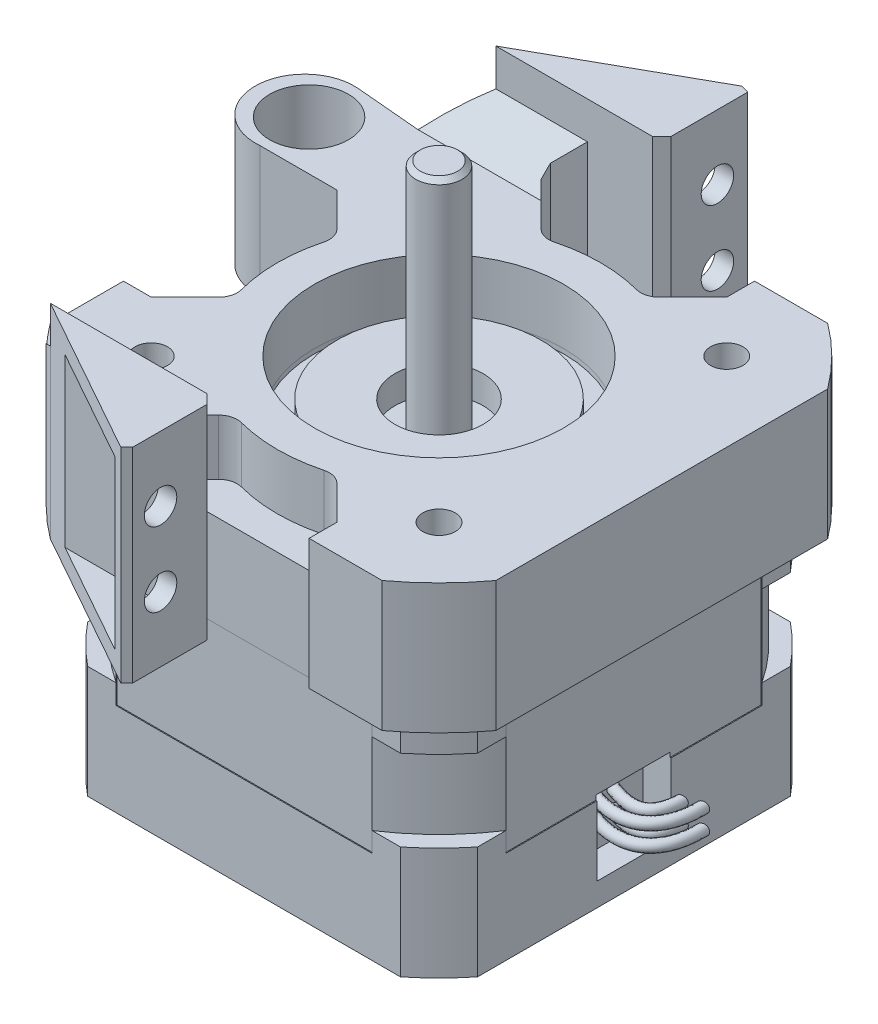
SolidWorks part; units mm, degrees
ref_plane "Front Plane" through (0, 0, 0) normal (0, 0, 1) x (1, 0, 0)
ref_plane "Top Plane" through (0, 0, 0) normal (0, 1, 0) x (1, 0, 0)
ref_plane "Right Plane" through (0, 0, 0) normal (1, 0, 0) x (0, 0, -1)
sketch "Sketch1" plane through (0, 0, 0) normal (0, 1, 0) x (1, 0, 0)
  line L0 (0, -21) -> (0, 21) construction
  line L1 (-21, 16.851) -> (-21, -16.851)
  line L2 (-16.851, -21) -> (16.851, -21)
  line L3 (21, -16.851) -> (21, 16.851)
  line L4 (16.851, 21) -> (-16.851, 21)
  line L5 (-21, 0) -> (21, 0) construction
  arc A0 (-21, 16.851) -> (-16.851, 21) centre (0, 0) cw
  arc A1 (16.851, 21) -> (21, 16.851) centre (0, 0) cw
  arc A2 (21, -16.851) -> (16.851, -21) centre (0, 0) cw
  arc A3 (-21, -16.851) -> (-16.851, -21) centre (0, 0) ccw
  dimension "D3" = 26.925
  dimension "D1" = 42
  dimension "D2" = 42
extrude "Boss-Extrude2" add sketch "Sketch1" along normal blind 33
sketch "Sketch3" plane through (0, 0, 0) normal (0, 0, 1) x (1, 0, 0)
  line L0 (0, -2.0131) -> (0, 34.8611) construction
  line L1 (-30.125, 20.875) -> (-25.125, 20.875)
  line L2 (-30.125, 20.875) -> (-30.125, 12.125)
  line L3 (-30.125, 12.125) -> (-25.125, 12.125)
  line L4 (-25.125, 20.875) -> (-25.125, 12.125)
  line L5 (21, 16.5) -> (-21, 16.5) construction
  line L6 (21, 33) -> (21, 0) construction
  line L7 (-21, 33) -> (-21, 0) construction
  point P13 (-25.125, 16.5)
  dimension "D1" = 8.75
  dimension "D2" = 25.125
  dimension "D3" = 5
revolve "Cut-Revolve1" cut sketch "Sketch3" angle 360 about L0
sketch "Sketch4" plane through (0, 33, 0) normal (0, 1, 0) x (1, 0, 0)
  circle A0 centre (0, 0) radius 13.425
  dimension "D1" = 26.85
extrude "Cut-Extrude1" cut sketch "Sketch4" against normal blind 0.5
sketch "Sketch5" plane through (0, 32.5, 0) normal (0, 1, 0) x (1, 0, 0)
  circle A0 centre (0, 0) radius 11
  dimension "D1" = 22
extrude "Boss-Extrude3" add sketch "Sketch5" along normal blind 2.5
sketch "Sketch6" plane through (0, 35, 0) normal (0, 1, 0) x (1, 0, 0)
  circle A0 centre (0, 0) radius 4.75
  dimension "D1" = 9.5
extrude "Cut-Extrude2" cut sketch "Sketch6" against normal blind 3
sketch "Sketch7" plane through (0, 32, 0) normal (0, 1, 0) x (1, 0, 0)
  circle A0 centre (0, 0) radius 2.5
  dimension "D1" = 5
extrude "Boss-Extrude4" add sketch "Sketch7" along normal blind 25.25
chamfer "Chamfer1" distance 0.5 angle 45 1 edges at (0, 57.25, 2.5)
sketch "Sketch8" plane through (0, 0, 0) normal (0, -1, 0) x (1, 0, 0)
  circle A0 centre (0, 0) radius 4.5
  dimension "D1" = 9
extrude "Cut-Extrude3" cut sketch "Sketch8" against normal blind 3
sketch "Sketch9" plane through (0, 33, 0) normal (0, 1, 0) x (1, 0, 0)
  line L0 (-15.5, 15.5) -> (15.5, 15.5) construction
  line L1 (15.5, 15.5) -> (15.5, -15.5) construction
  line L2 (15.5, -15.5) -> (-15.5, -15.5) construction
  line L3 (-15.5, -15.5) -> (-15.5, 15.5) construction
  point P2 (-15.5, 0)
  point P5 (0, 15.5)
  dimension "D1" = 31
  dimension "D2" = 31
hole_wizard "M3x0.5 Tapped Hole1" positions "Sketch11" profile "Sketch10" tap size "M3x0.5" standard "ANSI Metric"
sketch "Sketch11" plane through (0, 33, 0) normal (0, 1, 0) x (1, 0, 0)
  point P0 (-15.5, -15.5)
  point P3 (-15.5, 15.5)
  point P6 (15.5, 15.5)
  point P9 (15.5, -15.5)
sketch "Sketch10" plane through (-15.5, 33, 15.5) normal (1, 0, 0) x (0, 0, 1)
  line L0 (0, 0) -> (0, 5.2511)
  line L1 (0, 5.2511) -> (1.25, 4.5)
  line L2 (1.25, 4.5) -> (1.25, 0)
  line L5 (1.25, 0) -> (0, 0)
  line L10 (0, 5.2511) -> (-1.25, 4.5) construction
  line L11 (0, -6.35) -> (0, 107.95) construction
  dimension "Tap Drill Dia." = 2.5
  dimension "Tap Drill Depth" = 4.5
  dimension "Drill Angle" = 118
sketch "Sketch12" plane through (21, 0, 0) normal (1, 0, 0) x (0, 0, -1)
  line L0 (-16.851, 0) -> (16.851, 0) construction
  line L1 (-4, 10.5) -> (4, 10.5)
  line L2 (-4, 10.5) -> (-4, 2.5)
  line L3 (-4, 2.5) -> (4, 2.5)
  line L4 (4, 10.5) -> (4, 2.5)
  point P4 (0, 2.5)
  dimension "D1" = 8
  dimension "D2" = 8
  dimension "D3" = 2.5
extrude "Cut-Extrude4" cut sketch "Sketch12" against normal blind 3
sketch "Sketch13" plane through (18, 0, 0) normal (1, 0, 0) x (0, 0, -1)
  circle A0 centre (-1.1125, 7.415) radius 0.6
  circle A1 centre (0.707, 7.415) radius 0.6
  circle A2 centre (-1.1125, 5.3322) radius 0.6
  circle A3 centre (0.707, 5.3322) radius 0.6
  dimension "D1" = 1.2
sketch "Sketch14" plane through (0, 0, 0) normal (0, 1, 0) x (1, 0, 0)
  spline S0 degree 2 poles (17.6767, 0) (23.6461, -2.3668) (23.7984, 3.3576) knots 0 0 0 1 1 1
sweep "Sweep2" add profiles "Sketch13" path "Sketch14"
sketch "Sketch15" plane through (0, 0, -21) normal (0, 0, -1) x (-1, 0, 0)
  line L0 (-13.7937, 12.125) -> (-13.7937, 20.875) construction
  line L1 (-13.7937, 23) -> (13.7937, 23)
  line L2 (-13.7937, 23) -> (-13.7937, 10)
  line L3 (-13.7937, 10) -> (13.7937, 10)
  line L4 (13.7937, 23) -> (13.7937, 10)
  line L5 (13.7937, 20.875) -> (13.7937, 12.125) construction
  point P8 (-13.7937, 16.5)
  point P9 (-13.7937, 16.5)
  dimension "D1" = 13
extrude "Cut-Extrude5" cut sketch "Sketch15" against normal blind 0.1
ref_axis "Axis1" through (0, 0, 0) along (0, 1, 0)
pattern_circular "CirPattern1" count 4 over 360 about axis through (0, 0, 0) along (0, 1, 0) of "Cut-Extrude5"
ref_plane "Plane1" through (0, 33, 0) normal (0, 1, 0) x (1, 0, 0)
sketch "Sketch16" plane through (0, 33, 0) normal (0, 1, 0) x (1, 0, 0)
  line L0 (-10.001, -21) -> (-5.5264, -16.5254)
  line L1 (9.999, -21) -> (5.5249, -16.5259)
  line L2 (-21, -9.999) -> (-16.5259, -5.5249)
  line L3 (-16.5254, 5.5264) -> (-21, 10.001)
  line L4 (-21, 16.851) -> (-21, -16.851)
  line L5 (-16.851, -21) -> (16.851, -21)
  line L6 (21, -16.851) -> (21, 16.851)
  line L7 (16.851, 21) -> (-16.851, 21)
  line L8 (-21, 16.851) -> (-21, -16.851)
  line L9 (-16.851, -21) -> (16.851, -21)
  line L10 (21, -16.851) -> (21, 16.851)
  line L11 (16.851, 21) -> (-16.851, 21)
  line L12 (-10.001, 21) -> (-5.5264, 16.5254)
  line L13 (9.999, 21) -> (5.5249, 16.5259)
  circle A0 centre (0, 0) radius 13.425 construction
  circle A1 centre (0, 0) radius 13.425
  arc A4 (-16.851, 21) -> (-21, 16.851) centre (0, 0) ccw
  arc A5 (-21, -16.851) -> (-16.851, -21) centre (0, 0) ccw
  arc A6 (16.851, -21) -> (21, -16.851) centre (0, 0) ccw
  arc A7 (21, 16.851) -> (16.851, 21) centre (0, 0) ccw
  arc A8 (-16.851, 21) -> (-21, 16.851) centre (0, 0) ccw
  arc A9 (-21, -16.851) -> (-16.851, -21) centre (0, 0) ccw
  arc A10 (16.851, -21) -> (21, -16.851) centre (0, 0) ccw
  arc A11 (21, 16.851) -> (16.851, 21) centre (0, 0) ccw
  circle A12 centre (-15.5, -15.5) radius 1.25 construction
  circle A13 centre (15.5, -15.5) radius 1.25 construction
  circle A14 centre (15.5, 15.5) radius 1.25 construction
  circle A15 centre (-15.5, 15.5) radius 1.25 construction
  circle A16 centre (-15.5, -15.5) radius 1.25
  circle A17 centre (15.5, -15.5) radius 1.25
  circle A18 centre (15.5, 15.5) radius 1.25
  circle A19 centre (-15.5, 15.5) radius 1.25
  circle A20 centre (-15.5, 15.5) radius 1.75
  circle A21 centre (-15.5, -15.5) radius 1.75
  circle A22 centre (15.5, -15.5) radius 1.75
  circle A23 centre (15.5, 15.5) radius 1.75
  circle A24 centre (0, 0) radius 17.425
  dimension "D4" = 20
  dimension "D5" = 45
  dimension "D6" = 45
  dimension "D7" = 6.85
  dimension "D8" = 45
  dimension "D9" = 45
  dimension "D10" = 20
  dimension "D11" = 6.85
  dimension "D12" = 45
  dimension "D13" = 45
  dimension "D14" = 20
  dimension "D15" = 6.85
  dimension "D1" = 0
  dimension "D2" = 0.5
  dimension "D3" = 4
extrude "Boss-Extrude5" add sketch "Sketch16" along normal blind 6 separate body contours A24 L2 L8 A9 L9 L0 A21 | A24 A1 | A24 L12 L11 A8 L8 L3 A20 | A24 L1 L9 A10 L10 A11 L11 L13 A23 A22 region at (-13.426, 33, 20.7812) region at (-11.9734, 33, 11.9723) region at (8.0785, 33, 18.4465) region at (-18.608, 33, -7.9184)
sketch "Sketch17" plane through (0, 39, 0) normal (0, 1, 0) x (1, 0, 0)
  line L13 (-21, 10.001) -> (-24, 10.001)
  line L14 (-10.001, 21) -> (-10.001, 24)
  line L15 (9.999, 21) -> (9.999, 24)
  line L16 (-21, -9.999) -> (-24, -9.999)
  line L17 (-10.001, -21) -> (-10.001, -24)
  line L18 (9.999, -21) -> (9.999, -24)
  line L26 (-8.7583, -24) -> (-4.6476, -19.8892)
  line L27 (4.646, -19.8896) -> (8.7564, -24)
  line L28 (8.7564, -24) -> (17.8747, -24)
  line L29 (24, -17.8747) -> (24, 17.8747)
  line L30 (17.8747, 24) -> (8.7564, 24)
  line L31 (8.7564, 24) -> (4.646, 19.8896)
  line L32 (-4.6476, 19.8892) -> (-8.7583, 24)
  line L33 (-8.7583, 24) -> (-17.8747, 24)
  line L34 (-24, 17.8747) -> (-24, 8.7583)
  line L35 (-24, 8.7583) -> (-19.8892, 4.6476)
  line L36 (-19.8896, -4.646) -> (-24, -8.7564)
  line L37 (-24, -8.7564) -> (-24, -17.8747)
  line L38 (-17.8747, -24) -> (-8.7583, -24)
  line L39 (-8.7583, -24) -> (-4.6476, -19.8892)
  line L40 (4.646, -19.8896) -> (8.7564, -24)
  line L41 (8.7564, -24) -> (17.8747, -24)
  line L42 (24, -17.8747) -> (24, 17.8747)
  line L43 (17.8747, 24) -> (8.7564, 24)
  line L44 (8.7564, 24) -> (4.646, 19.8896)
  line L45 (-4.6476, 19.8892) -> (-8.7583, 24)
  line L46 (-8.7583, 24) -> (-17.8747, 24)
  line L47 (-24, 17.8747) -> (-24, 8.7583)
  line L48 (-24, 8.7583) -> (-19.8892, 4.6476)
  line L49 (-19.8896, -4.646) -> (-24, -8.7564)
  line L50 (-24, -8.7564) -> (-24, -17.8747)
  line L51 (-17.8747, -24) -> (-8.7583, -24)
  line L71 (-9.7939, -21.5) -> (-5.3895, -17.0956)
  line L72 (5.388, -17.0961) -> (9.7919, -21.5)
  line L73 (9.7919, -21.5) -> (17.0259, -21.5)
  line L74 (21.5, -17.0259) -> (21.5, 17.0259)
  line L75 (17.0259, 21.5) -> (9.7919, 21.5)
  line L76 (9.7919, 21.5) -> (5.388, 17.0961)
  line L77 (-5.3895, 17.0956) -> (-9.7939, 21.5)
  line L78 (-9.7939, 21.5) -> (-17.0259, 21.5)
  line L79 (-21.5, 17.0259) -> (-21.5, 9.7939)
  line L80 (-21.5, 9.7939) -> (-17.0956, 5.3895)
  line L81 (-17.0961, -5.388) -> (-21.5, -9.7919)
  line L82 (-21.5, -9.7919) -> (-21.5, -17.0259)
  line L83 (-17.0259, -21.5) -> (-9.7939, -21.5)
  line L84 (-9.7939, -21.5) -> (-5.3895, -17.0956)
  line L85 (5.388, -17.0961) -> (9.7919, -21.5)
  line L86 (9.7919, -21.5) -> (17.0259, -21.5)
  line L87 (21.5, -17.0259) -> (21.5, 17.0259)
  line L88 (17.0259, 21.5) -> (9.7919, 21.5)
  line L89 (9.7919, 21.5) -> (5.388, 17.0961)
  line L90 (-5.3895, 17.0956) -> (-9.7939, 21.5)
  line L91 (-9.7939, 21.5) -> (-17.0259, 21.5)
  line L92 (-21.5, 17.0259) -> (-21.5, 9.7939)
  line L93 (-21.5, 9.7939) -> (-17.0956, 5.3895)
  line L94 (-17.0961, -5.388) -> (-21.5, -9.7919)
  line L95 (-21.5, -9.7919) -> (-21.5, -17.0259)
  line L96 (-17.0259, -21.5) -> (-9.7939, -21.5)
  arc A14 (-4.6476, -19.8892) -> (4.646, -19.8896) centre (0, 0) ccw
  arc A15 (17.8747, -24) -> (24, -17.8747) centre (0, 0) ccw
  arc A16 (24, 17.8747) -> (17.8747, 24) centre (0, 0) ccw
  arc A17 (4.646, 19.8896) -> (-4.6476, 19.8892) centre (0, 0) ccw
  arc A18 (-17.8747, 24) -> (-24, 17.8747) centre (0, 0) ccw
  arc A19 (-19.8892, 4.6476) -> (-19.8896, -4.646) centre (0, 0) ccw
  arc A20 (-24, -17.8747) -> (-17.8747, -24) centre (0, 0) ccw
  arc A21 (-4.6476, -19.8892) -> (4.646, -19.8896) centre (0, 0) ccw
  arc A22 (17.8747, -24) -> (24, -17.8747) centre (0, 0) ccw
  arc A23 (24, 17.8747) -> (17.8747, 24) centre (0, 0) ccw
  arc A24 (4.646, 19.8896) -> (-4.6476, 19.8892) centre (0, 0) ccw
  arc A25 (-17.8747, 24) -> (-24, 17.8747) centre (0, 0) ccw
  arc A26 (-19.8892, 4.6476) -> (-19.8896, -4.646) centre (0, 0) ccw
  arc A27 (-24, -17.8747) -> (-17.8747, -24) centre (0, 0) ccw
  arc A36 (-5.3895, -17.0956) -> (5.388, -17.0961) centre (0, 0) ccw
  arc A37 (17.0259, -21.5) -> (21.5, -17.0259) centre (0, 0) ccw
  arc A38 (21.5, 17.0259) -> (17.0259, 21.5) centre (0, 0) ccw
  arc A39 (5.388, 17.0961) -> (-5.3895, 17.0956) centre (0, 0) ccw
  arc A40 (-17.0259, 21.5) -> (-21.5, 17.0259) centre (0, 0) ccw
  arc A41 (-17.0956, 5.3895) -> (-17.0961, -5.388) centre (0, 0) ccw
  arc A42 (-21.5, -17.0259) -> (-17.0259, -21.5) centre (0, 0) ccw
  arc A43 (-5.3895, -17.0956) -> (5.388, -17.0961) centre (0, 0) ccw
  arc A44 (17.0259, -21.5) -> (21.5, -17.0259) centre (0, 0) ccw
  arc A45 (21.5, 17.0259) -> (17.0259, 21.5) centre (0, 0) ccw
  arc A46 (5.388, 17.0961) -> (-5.3895, 17.0956) centre (0, 0) ccw
  arc A47 (-17.0259, 21.5) -> (-21.5, 17.0259) centre (0, 0) ccw
  arc A48 (-17.0956, 5.3895) -> (-17.0961, -5.388) centre (0, 0) ccw
  arc A49 (-21.5, -17.0259) -> (-17.0259, -21.5) centre (0, 0) ccw
  line M24 (9.999, -21) -> (16.851, -21)
  arc M25 (16.851, -21) -> (21, -16.851) centre (0, 0) ccw
  line M26 (21, -16.851) -> (21, 16.851)
  arc M27 (21, 16.851) -> (16.851, 21) centre (0, 0) ccw
  line M28 (16.851, 21) -> (9.999, 21)
  line M32 (-10.001, 21) -> (-16.851, 21)
  arc M33 (-16.851, 21) -> (-21, 16.851) centre (0, 0) ccw
  line M34 (-21, 16.851) -> (-21, 10.001)
  line M38 (-21, -9.999) -> (-21, -16.851)
  arc M39 (-21, -16.851) -> (-16.851, -21) centre (0, 0) ccw
  line M40 (-16.851, -21) -> (-10.001, -21)
  dimension "D1" = 3
  dimension "D2" = 0.5
extrude "Boss-Extrude6" add sketch "Sketch17" against normal blind 14 separate body contours L46 A25 L47 L13 L14 M34 M33 M32 | L50 A27 L51 L17 L16 M40 M39 M38 | L42 A23 L43 L15 L18 L41 A22 M28 M27 M26 M25 M24 region at (-22.75, 39, -10.199) region at (-21.698, 39, 13.5124) region at (10.499, 39, -22.75)
fillet "Fillet1" radius 2 6 edges at (5.5249, 36, 16.5259) (-5.5264, 36, 16.5254) (-16.5259, 36, 5.5249) (-16.5254, 36, -5.5264) (5.5249, 36, -16.5259) (-5.5264, 36, -16.5254)
extrude "Boss-Extrude7" add sketch "Sketch17<4>" against normal up to vertex (6 mm away) separate body contours L95 A49 L96 L17 L16 M40 M39 M38 | L91 A47 L92 L13 L14 M34 M33 M32 | L87 A45 L88 L15 L18 L86 A44 M28 M27 M26 M25 M24 region at (-21.25, 39, -10.1636) region at (-21.25, 39, 10.1617) region at (13.5124, 39, -21.0549) up to point (-17.3686, 33, 6.3676)
sketch "Sketch17<4>" plane through (0, 39, 0) normal (0, 1, 0) x (1, 0, 0) same geometry as "Sketch17"
combine bodies "Combine2" operation type add bodies to combine 115 122 121 114 116 117 120
sketch "Sketch18" plane through (0, 39, 0) normal (0, 1, 0) x (1, 0, 0)
  line L0 (-10.001, 24) -> (-0.001, 24)
  line L1 (-0.001, 24) -> (-0.001, 34)
  line L3 (-17.8747, 24) -> (-0.001, 34)
  line L4 (-17.8747, -24) -> (-0.001, -24)
  line L5 (-10.001, -21) -> (-10.001, -24) construction
  line L6 (-0.001, -24) -> (-0.001, -34)
  line L7 (-0.001, -34) -> (-17.8747, -24)
  line L23 (9.999, 24) -> (9.999, 21)
  line L24 (9.999, 21) -> (6.3676, 17.3686)
  line L25 (-6.3692, 17.3682) -> (-10.001, 21)
  line L26 (-10.001, 21) -> (-10.001, 24)
  line L27 (-10.001, 24) -> (-17.8747, 24)
  line L28 (-24, 17.8747) -> (-24, 10.001)
  line L29 (-24, 10.001) -> (-21, 10.001)
  line L30 (-21, 10.001) -> (-17.3682, 6.3692)
  line L31 (-17.3686, -6.3676) -> (-21, -9.999)
  line L32 (-21, -9.999) -> (-24, -9.999)
  line L33 (-24, -9.999) -> (-24, -17.8747)
  line L34 (-17.8747, -24) -> (-10.001, -24)
  line L35 (-10.001, -24) -> (-10.001, -21)
  line L36 (-10.001, -21) -> (-6.3692, -17.3682)
  line L37 (6.3676, -17.3686) -> (9.999, -21)
  line L38 (9.999, -21) -> (9.999, -24)
  line L39 (9.999, -24) -> (17.8747, -24)
  line L40 (24, -17.8747) -> (24, 17.8747)
  line L41 (17.8747, 24) -> (9.999, 24)
  line L46 (-10.001, 24) -> (-17.8747, 24)
  arc A15 (4.4434, 16.8489) -> (6.3676, 17.3686) centre (4.9534, 18.7828) ccw
  arc A16 (4.4434, 16.8489) -> (-4.4448, 16.8486) centre (0, 0) ccw
  arc A17 (-6.3692, 17.3682) -> (-4.4448, 16.8486) centre (-4.955, 18.7824) ccw
  arc A18 (-17.8747, 24) -> (-24, 17.8747) centre (0, 0) ccw
  arc A19 (-16.8486, 4.4448) -> (-17.3682, 6.3692) centre (-18.7824, 4.955) ccw
  arc A20 (-16.8486, 4.4448) -> (-16.8489, -4.4434) centre (0, 0) ccw
  arc A21 (-17.3686, -6.3676) -> (-16.8489, -4.4434) centre (-18.7828, -4.9534) ccw
  arc A22 (-24, -17.8747) -> (-17.8747, -24) centre (0, 0) ccw
  arc A23 (-4.4448, -16.8486) -> (-6.3692, -17.3682) centre (-4.955, -18.7824) ccw
  arc A24 (-4.4448, -16.8486) -> (4.4434, -16.8489) centre (0, 0) ccw
  arc A25 (6.3676, -17.3686) -> (4.4434, -16.8489) centre (4.9534, -18.7828) ccw
  arc A26 (17.8747, -24) -> (24, -17.8747) centre (0, 0) ccw
  arc A27 (24, 17.8747) -> (17.8747, 24) centre (0, 0) ccw
  dimension "D3" = 10
  dimension "D1" = 10
  dimension "D2" = 10
  dimension "D4" = 10
  dimension "D5" = 0
extrude "Boss-Extrude8" add sketch "Sketch18" against normal up to surface (14 mm away) up to face at (-18.2819, 25, -18.2819)
sketch "Sketch19" plane through (-0.001, 0, 0) normal (1, 0, 0) x (0, 0, -1)
  line L0 (34, 25) -> (34, 39) construction
  line L1 (34, 27) -> (26, 27)
  line L2 (34, 27) -> (34, 37)
  line L3 (34, 37) -> (26, 37)
  line L4 (26, 27) -> (26, 37)
  line L5 (24, 39) -> (34, 39) construction
  line L6 (-34, 25) -> (-34, 39) construction
  line L7 (-34, 37) -> (-26, 37)
  line L8 (-34, 37) -> (-34, 27)
  line L9 (-34, 27) -> (-26, 27)
  line L10 (-26, 37) -> (-26, 27)
  line L11 (-34, 39) -> (-24, 39) construction
  circle A0 centre (30, 32) radius 1.75
  circle A1 centre (-30, 32) radius 1.75
  point P19 (34, 32)
  point P20 (-34, 32)
  point P21 (30, 27)
  point P25 (-30, 27)
  dimension "D7" = 3.5
  dimension "D8" = 3.5
  dimension "D1" = 10
  dimension "D2" = 2
  dimension "D3" = 8
  dimension "D4" = 8
  dimension "D5" = 10
  dimension "D6" = 2
ref_plane "Plane2" through (-2.001, 0, 0) normal (1, 0, 0) x (0, 0, -1)
sketch "Sketch20" plane through (-2.001, 0, 0) normal (1, 0, 0) x (0, 0, -1)
  line L0 (34, 27) -> (34, 37) construction
  line L1 (34, 37) -> (26, 37) construction
  line L2 (34, 27) -> (26, 27) construction
  line L3 (26, 27) -> (26, 37) construction
  line L4 (-34, 37) -> (-34, 27) construction
  line L5 (-34, 37) -> (-26, 37) construction
  line L6 (-26, 37) -> (-26, 27) construction
  line L7 (-34, 27) -> (-26, 27) construction
  line L8 (34, 27) -> (34, 37)
  line L9 (34, 37) -> (26, 37)
  line L10 (34, 27) -> (26, 27)
  line L11 (26, 27) -> (26, 37)
  line L12 (-34, 37) -> (-34, 27)
  line L13 (-34, 37) -> (-26, 37)
  line L14 (-26, 37) -> (-26, 27)
  line L15 (-34, 27) -> (-26, 27)
  circle A0 centre (-30, 32) radius 1.75 construction
  circle A1 centre (30, 32) radius 1.75 construction
  circle A2 centre (-30, 32) radius 1.75
  circle A3 centre (30, 32) radius 1.75
extrude "Cut-Extrude7" cut sketch "Sketch20" against normal blind 34 contours L12 L15 L14 L13 A2 | A2 | L10 L11 L9 L8 region at (-2.001, 36.8719, 30)
chamfer "Chamfer2" distance 2 angle 45 2 edges at (-10.001, 32, 24) (-10.001, 32, -24)
ref_plane "Plane3" [suppressed] through (-2.001, 37, 32.881) normal (0, 0, 1) x (1, 0, 0)
extrude "Cut-Extrude10" cut sketch "Sketch19" against normal blind 10 contours A0 | A1
sketch "Sketch21" plane through (0, 39, 0) normal (0, 1, 0) x (1, 0, 0)
  line L0 (-17.8747, -24) -> (-8.001, -24)
  line L1 (-8.001, 24) -> (-17.8747, 24)
  line L25 (9.999, 24) -> (9.999, 21)
  line L26 (9.999, 21) -> (6.3676, 17.3686)
  line L27 (-6.3692, 17.3682) -> (-10.001, 21)
  line L28 (-10.001, 21) -> (-10.001, 22)
  line L29 (-10.001, 22) -> (-8.001, 24)
  line L30 (-8.001, 24) -> (-0.001, 24)
  line L31 (-0.001, 24) -> (-0.001, 34)
  line L32 (-0.001, 34) -> (-17.8747, 24)
  line L33 (-24, 17.8747) -> (-24, 10.001)
  line L34 (-24, 10.001) -> (-21, 10.001)
  line L35 (-21, 10.001) -> (-17.3682, 6.3692)
  line L36 (-17.3686, -6.3676) -> (-21, -9.999)
  line L37 (-21, -9.999) -> (-24, -9.999)
  line L38 (-24, -9.999) -> (-24, -17.8747)
  line L39 (-17.8747, -24) -> (-0.001, -34)
  line L40 (-0.001, -34) -> (-0.001, -24)
  line L41 (-0.001, -24) -> (-8.001, -24)
  line L42 (-8.001, -24) -> (-10.001, -22)
  line L43 (-10.001, -22) -> (-10.001, -21)
  line L44 (-10.001, -21) -> (-6.3692, -17.3682)
  line L45 (6.3676, -17.3686) -> (9.999, -21)
  line L46 (9.999, -21) -> (9.999, -24)
  line L47 (9.999, -24) -> (17.8747, -24)
  line L48 (24, -17.8747) -> (24, 17.8747)
  line L49 (17.8747, 24) -> (9.999, 24)
  line L50 (9.999, 24) -> (9.999, 21)
  line L51 (9.999, 21) -> (6.3676, 17.3686)
  line L52 (-6.3692, 17.3682) -> (-10.001, 21)
  line L53 (-10.001, 21) -> (-10.001, 22)
  line L54 (-10.001, 22) -> (-8.001, 24)
  line L55 (-8.001, 24) -> (-0.001, 24)
  line L56 (-0.001, 24) -> (-0.001, 34)
  line L57 (-0.001, 34) -> (-17.8747, 24)
  line L58 (-24, 17.8747) -> (-24, 10.001)
  line L59 (-24, 10.001) -> (-21, 10.001)
  line L60 (-21, 10.001) -> (-17.3682, 6.3692)
  line L61 (-17.3686, -6.3676) -> (-21, -9.999)
  line L62 (-21, -9.999) -> (-24, -9.999)
  line L63 (-24, -9.999) -> (-24, -17.8747)
  line L64 (-17.8747, -24) -> (-0.001, -34)
  line L65 (-0.001, -34) -> (-0.001, -24)
  line L66 (-0.001, -24) -> (-8.001, -24)
  line L67 (-8.001, -24) -> (-10.001, -22)
  line L68 (-10.001, -22) -> (-10.001, -21)
  line L69 (-10.001, -21) -> (-6.3692, -17.3682)
  line L70 (6.3676, -17.3686) -> (9.999, -21)
  line L71 (9.999, -21) -> (9.999, -24)
  line L72 (9.999, -24) -> (17.8747, -24)
  line L73 (24, -17.8747) -> (24, 17.8747)
  line L74 (17.8747, 24) -> (9.999, 24)
  arc A13 (4.4434, 16.8489) -> (6.3676, 17.3686) centre (4.9534, 18.7828) ccw
  arc A14 (4.4434, 16.8489) -> (-4.4448, 16.8486) centre (0, 0) ccw
  arc A15 (-6.3692, 17.3682) -> (-4.4448, 16.8486) centre (-4.955, 18.7824) ccw
  arc A16 (-17.8747, 24) -> (-24, 17.8747) centre (0, 0) ccw
  arc A17 (-16.8486, 4.4448) -> (-17.3682, 6.3692) centre (-18.7824, 4.955) ccw
  arc A18 (-16.8486, 4.4448) -> (-16.8489, -4.4434) centre (0, 0) ccw
  arc A19 (-17.3686, -6.3676) -> (-16.8489, -4.4434) centre (-18.7828, -4.9534) ccw
  arc A20 (-24, -17.8747) -> (-17.8747, -24) centre (0, 0) ccw
  arc A21 (-4.4448, -16.8486) -> (-6.3692, -17.3682) centre (-4.955, -18.7824) ccw
  arc A22 (-4.4448, -16.8486) -> (4.4434, -16.8489) centre (0, 0) ccw
  arc A23 (6.3676, -17.3686) -> (4.4434, -16.8489) centre (4.9534, -18.7828) ccw
  arc A24 (17.8747, -24) -> (24, -17.8747) centre (0, 0) ccw
  arc A25 (24, 17.8747) -> (17.8747, 24) centre (0, 0) ccw
  arc A26 (4.4434, 16.8489) -> (6.3676, 17.3686) centre (4.9534, 18.7828) ccw
  arc A27 (4.4434, 16.8489) -> (-4.4448, 16.8486) centre (0, 0) ccw
  arc A28 (-6.3692, 17.3682) -> (-4.4448, 16.8486) centre (-4.955, 18.7824) ccw
  arc A29 (-17.8747, 24) -> (-24, 17.8747) centre (0, 0) ccw
  arc A30 (-16.8486, 4.4448) -> (-17.3682, 6.3692) centre (-18.7824, 4.955) ccw
  arc A31 (-16.8486, 4.4448) -> (-16.8489, -4.4434) centre (0, 0) ccw
  arc A32 (-17.3686, -6.3676) -> (-16.8489, -4.4434) centre (-18.7828, -4.9534) ccw
  arc A33 (-24, -17.8747) -> (-17.8747, -24) centre (0, 0) ccw
  arc A34 (-4.4448, -16.8486) -> (-6.3692, -17.3682) centre (-4.955, -18.7824) ccw
  arc A35 (-4.4448, -16.8486) -> (4.4434, -16.8489) centre (0, 0) ccw
  arc A36 (6.3676, -17.3686) -> (4.4434, -16.8489) centre (4.9534, -18.7828) ccw
  arc A37 (17.8747, -24) -> (24, -17.8747) centre (0, 0) ccw
  arc A38 (24, 17.8747) -> (17.8747, 24) centre (0, 0) ccw
  line M47 (-8.001, 24) -> (-0.001, 24)
  line M48 (-0.001, 24) -> (-0.001, 34)
  line M49 (-0.001, 34) -> (-17.8747, 24)
  line M61 (-17.8747, -24) -> (-0.001, -34)
  line M62 (-0.001, -34) -> (-0.001, -24)
  line M63 (-0.001, -24) -> (-8.001, -24)
  dimension "D1" = 0
extrude "Boss-Extrude9" add sketch "Sketch21" along normal blind 8 contours L0 M61 M62 M63 | L1 M47 M48 M49 region at (-5.9589, 39, 27.3333) region at (-5.9589, 39, -27.3333)
sketch "Sketch22" plane through (0, 37, 0) normal (0, -1, 0) x (1, 0, 0)
  line L0 (-14.3, -26) -> (-2.001, -32.881) construction
  line L1 (-2.001, -32.881) -> (-2.001, -26) construction
  line L2 (-2.001, -26) -> (-14.3, -26) construction
  line L3 (-14.3, 26) -> (-2.001, 26) construction
  line L4 (-2.001, 26) -> (-2.001, 32.881) construction
  line L5 (-2.001, 32.881) -> (-14.3, 26) construction
  line L6 (-14.3, -26) -> (-2.001, -32.881)
  line L7 (-2.001, -32.881) -> (-2.001, -26)
  line L8 (-2.001, -26) -> (-14.3, -26)
  line L9 (-14.3, 26) -> (-2.001, 26)
  line L10 (-2.001, 26) -> (-2.001, 32.881)
  line L11 (-2.001, 32.881) -> (-14.3, 26)
extrude "Cut-Extrude11" cut sketch "Sketch22" against normal blind 8
sketch "Sketch23" plane through (-2.001, 0, 0) normal (-1, 0, 0) x (0, 0, 1)
  line L0 (26, 45) -> (32.881, 45) construction
  line L1 (26, 45) -> (26, 27) construction
  line L2 (-32.881, 45) -> (-26, 45) construction
  line L3 (-26, 27) -> (-26, 45) construction
  circle A0 centre (30, 40) radius 1.75
  circle A3 centre (-30, 40) radius 1.75
  dimension "D1" = 5
  dimension "D2" = 4
  dimension "D3" = 3.5
  dimension "D4" = 3.5
  dimension "D5" = 5
  dimension "D6" = 4
extrude "Cut-Extrude13" cut sketch "Sketch23" against normal up to surface (2 mm away) up to face at (-0.001, 32, -31.75)
chamfer "Chamfer3" distance 4 angle 45 2 edges at (-12.9379, 39, -24) (-12.9379, 39, 24)
chamfer "Chamfer4" distance 1 angle 45 4 edges at (-0.001, 36, -34) (-0.001, 36, 34) (-0.001, 36, -24) (-0.001, 36, 24) first distance on face at (-8.1505, 36, -29.4405) first distance on face at (-0.001, 40, 28.25) first distance on face at (-0.001, 40, -31.75)
sketch "Sketch24" plane through (0, 39, 0) normal (0, 1, 0) x (1, 0, 0)
  line L1 (-29.3098, 10.001) -> (-24, 10.001)
  line L2 (-24, 10.001) -> (-24, 17.8747)
  line L3 (-24, 17.8747) -> (-22.26, 20)
  line L4 (-22.26, 20) -> (-29.3098, 20.6206)
  circle A4 centre (-29.3098, 15.3108) radius 4.25
  circle A5 centre (-29.3098, 15.3108) radius 5.3098
  arc A6 (-29.3098, 20.6206) -> (-29.3098, 10.001) centre (-29.7772, 15.3108) ccw
  dimension "D1" = 8.5
extrude "Boss-Extrude11" add sketch "Sketch24" against normal blind 14 contours A6 L1 L2 L3 L4
extrude "Cut-Extrude16" cut sketch "Sketch24<6>" against normal blind 14 contours A4 region at (-29.3098, 39, -15.3108)
sketch "Sketch24<6>" plane through (0, 39, 0) normal (0, 1, 0) x (1, 0, 0) same geometry as "Sketch24"
